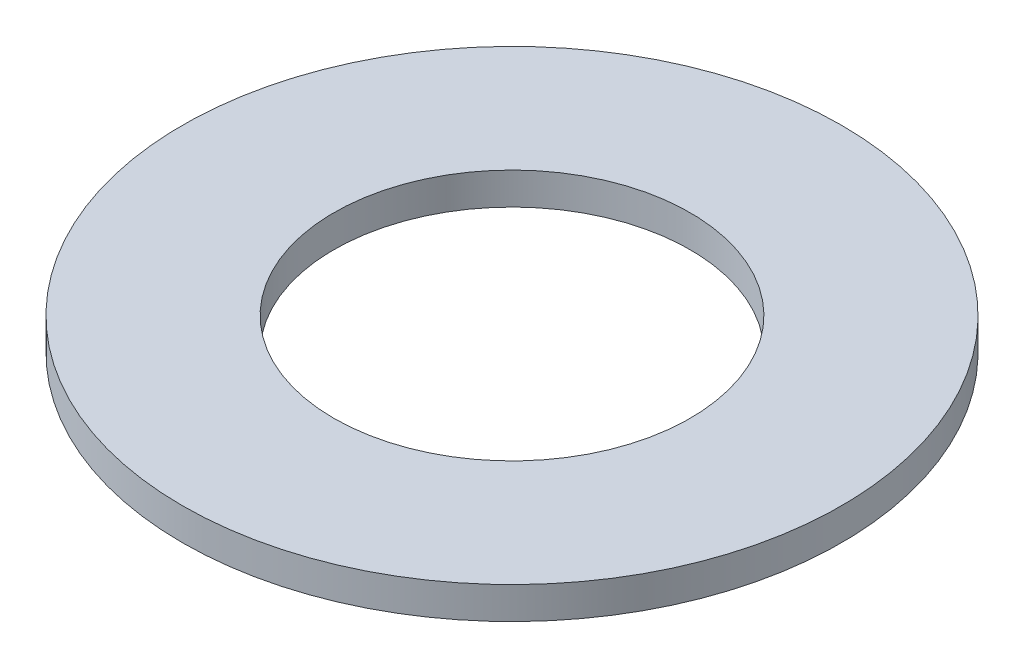
SolidWorks part; units mm, degrees
ref_plane "Front Plane" through (0, 0, 0) normal (0, 0, 1) x (1, 0, 0)
ref_plane "Top Plane" through (0, 0, 0) normal (0, 1, 0) x (1, 0, 0)
ref_plane "Right Plane" through (0, 0, 0) normal (1, 0, 0) x (0, 0, -1)
sketch "Sketch1" plane through (0, 0, 0) normal (0, 1, 0) x (1, 0, 0)
  circle A0 centre (0, 0) radius 92.5
  dimension "FLANGE_OD" = 185
extrude "Boss-Extrude1" add sketch "Sketch1" along normal blind 9
sketch "Sketch2" plane through (0, 0, 0) normal (0, 1, 0) x (1, 0, 0)
  circle A0 centre (0, 0) radius 50
  dimension "BORE_D" = 100
extrude "Cut-Extrude1" cut sketch "Sketch2" along normal through all
sketch "Sketch3" plane through (0, 9, 0) normal (0, 1, 0) x (1, 0, 0)
  circle A0 centre (0, 0) radius 37.0534 construction
  circle A1 centre (-37.0534, 0) radius 7.1037
  dimension "BOLT_D" = 14.2074
  dimension "BOLT_PCD" = 74.1067
extrude "Cut-Extrude2" cut sketch "Sketch3" against normal blind 7.0883 rebuild error yes
pattern_circular "CirPattern1" count 5 over 360 rebuild error yes
